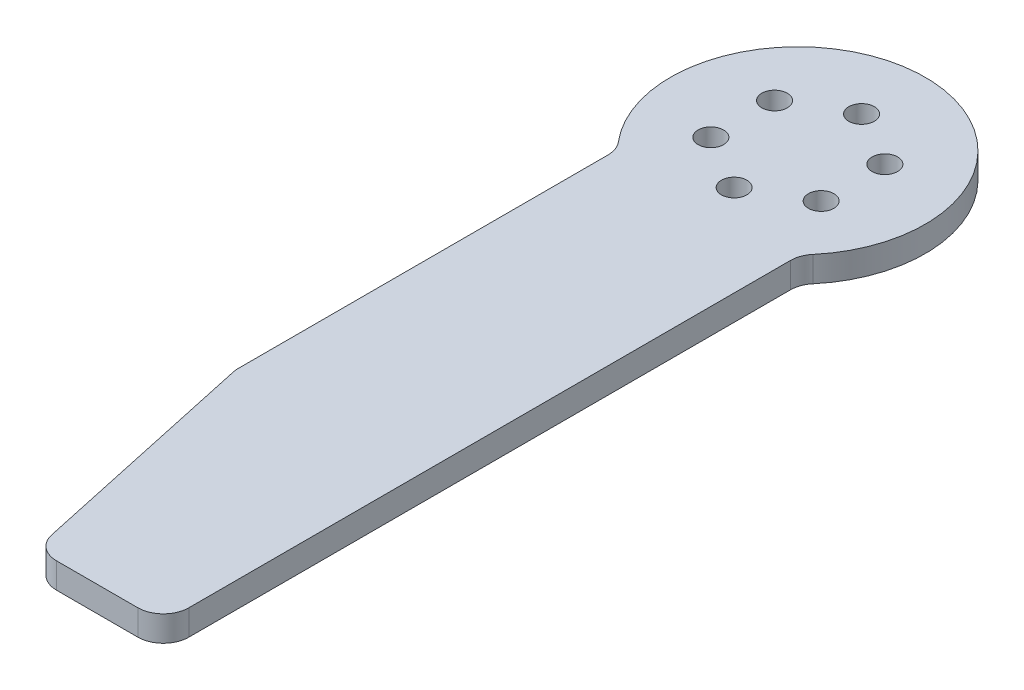
SolidWorks part; units mm, degrees
ref_plane "Front Plane" through (0, 0, 0) normal (0, 0, 1) x (1, 0, 0)
ref_plane "Top Plane" through (0, 0, 0) normal (0, 1, 0) x (1, 0, 0)
ref_plane "Right Plane" through (0, 0, 0) normal (1, 0, 0) x (0, 0, -1)
sketch "Sketch1" plane through (0, 0, 0) normal (0, 1, 0) x (1, 0, 0)
  line L0 (-9.1007, -8.8581) -> (-9.1007, -46.9581)
  line L1 (-9.1007, -46.9581) -> (-3.5993, -72.3581)
  line L2 (-3.5993, -72.3581) -> (9.1007, -72.3581)
  line L3 (9.1007, -72.3581) -> (9.1007, -8.8581)
  line L6 (-9.1007, -8.8581) -> (9.1007, -8.8581) construction
  line L7 (0, -8.8581) -> (0, 0) construction
  arc A0 (9.1007, -8.8581) -> (-9.1007, -8.8581) centre (0, 0) ccw
  circle A1 centre (0, 0) radius 6.35 construction
  circle A2 centre (0, 6.35) radius 1.27
  circle A3 centre (5.4993, 3.175) radius 1.27
  circle A4 centre (5.4993, -3.175) radius 1.27
  circle A5 centre (0, -6.35) radius 1.27
  circle A6 centre (-5.4993, -3.175) radius 1.27
  circle A7 centre (-5.4993, 3.175) radius 1.27
  point P19 (0, 0)
  dimension "D2" = 2.54
  dimension "D3" = 25.4
  dimension "D4" = 12.7
  dimension "D5" = 38.1
  dimension "D6" = 63.5
  dimension "D7" = 18.2015
  dimension "D8" = 12.7
  dimension "D1" = 6
extrude "Boss-Extrude1" add sketch "Sketch1" along normal blind 2.54
fillet "Fillet1" radius 2.54 5 edges at (-3.5993, 1.27, 72.3581) (9.1007, 1.27, 72.3581) (-9.1007, 1.27, 46.9581) (-9.1007, 1.27, 8.8581) (9.1007, 1.27, 8.8581)
